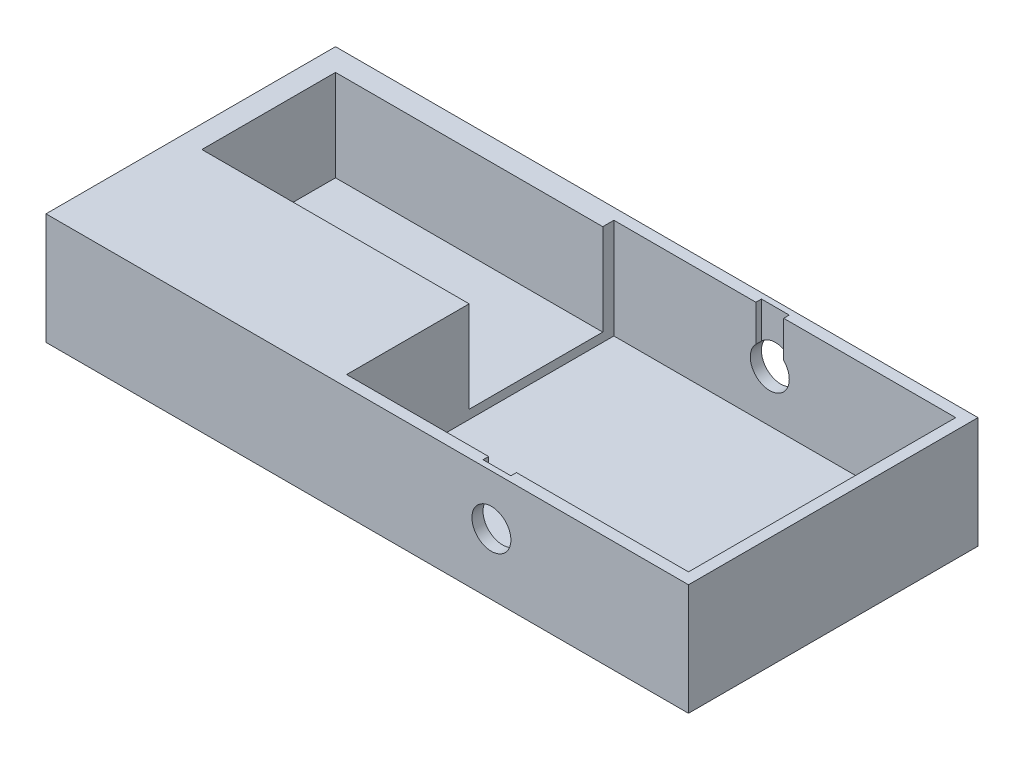
SolidWorks part; units mm, degrees
ref_plane "Front" through (0, 0, 0) normal (0, 0, 1) x (1, 0, 0)
ref_plane "Top" through (0, 0, 0) normal (0, 1, 0) x (1, 0, 0)
ref_plane "Right" through (0, 0, 0) normal (1, 0, 0) x (0, 0, -1)
sketch "Sketch1" plane through (0, 0, 0) normal (0, 1, 0) x (1, 0, 0)
  line L1 (-41.529, 33.02) -> (41.529, 33.02)
  line L2 (-41.529, 33.02) -> (-41.529, -33.02)
  line L3 (-41.529, -33.02) -> (41.529, -33.02)
  line L4 (41.529, 33.02) -> (41.529, -33.02)
  line L5 (-41.529, 33.02) -> (41.529, -33.02) construction
  line L6 (-41.529, -33.02) -> (41.529, 33.02) construction
  line L7 (-38.989, 30.48) -> (38.989, 30.48)
  line L8 (-38.989, 30.48) -> (-38.989, -30.48)
  line L9 (-38.989, -30.48) -> (38.989, -30.48)
  line L10 (38.989, 30.48) -> (38.989, -30.48)
  line L11 (-38.989, 30.48) -> (38.989, -30.48) construction
  line L12 (-38.989, -30.48) -> (38.989, 30.48) construction
  point P0 (0, 0)
  point P6 (0, 0)
  dimension "D1" = 66.04
  dimension "D2" = 83.058
  dimension "D3" = 60.96
  dimension "D4" = 77.978
extrude "pcb-base" add sketch "Sketch1" along normal blind 2.54 contours L8 L7 L10 L9
extrude "pcb-wall" add sketch "Sketch1<4>" along normal blind 25.4
sketch "Sketch1<4>" plane through (0, 0, 0) normal (0, 1, 0) x (1, 0, 0) same geometry as "Sketch1"
sketch "Sketch2" plane through (-41.529, 0, 0) normal (-1, 0, 0) x (0, 0, 1)
  line L1 (-27.94, 4.572) -> (2.54, 4.572)
  line L5 (-27.94, 25.4) -> (-27.94, 4.572)
  line L6 (2.54, 25.4) -> (33.02, 25.4)
  line L7 (33.02, 25.4) -> (33.02, 0) construction
  line L9 (-33.02, 0) -> (33.02, 0) construction
  line L11 (2.54, 4.572) -> (2.54, 25.4)
  line L13 (-33.02, 25.4) -> (33.02, 25.4) construction
  line L14 (33.02, 25.4) -> (33.02, 0)
  line L15 (-33.02, 0) -> (33.02, 0)
  line L16 (33.02, 0) -> (33.02, 25.4)
  line L17 (33.02, 25.4) -> (-33.02, 25.4)
  line L18 (-33.02, 25.4) -> (-33.02, 0)
  line L19 (-33.02, 0) -> (33.02, 0)
  line L23 (-33.02, 25.4) -> (-33.02, 0)
  line L24 (-27.94, 25.4) -> (-33.02, 25.4)
  point P0 (-12.7, 13.462)
  dimension "D1" = 5.08
  dimension "D2" = 30.48
  dimension "0.175" = 4.572
  dimension "D5" = 0
sketch "Sketch3" plane through (0, 0, -30.48) normal (0, 0, 1) x (1, 0, 0)
  line L0 (-38.989, 25.4) -> (-38.989, 2.54) construction
  line L2 (-6.604, 13.97) -> (-0.254, 13.97)
  line L3 (38.989, 25.4) -> (-38.989, 25.4) construction
  line L4 (-6.604, 13.97) -> (-6.604, 25.4)
  line L5 (-6.604, 25.4) -> (-0.254, 25.4)
  line L6 (-0.254, 13.97) -> (-0.254, 25.4)
  line L7 (-6.604, 13.97) -> (-0.254, 25.4) construction
  line L8 (-6.604, 25.4) -> (-0.254, 13.97) construction
  circle A0 centre (-3.429, 13.97) radius 4.445
  point P7 (-3.429, 19.685)
  line M4 (38.989, 25.4) -> (-38.989, 25.4)
  dimension "D2" = 8.89
  dimension "D1" = 35.56
  dimension "D3" = 11.43
  dimension "D4" = 6.35
sketch "Sketch4" plane through (0, 0, 30.48) normal (0, 0, -1) x (-1, 0, 0)
  line L0 (38.989, 25.4) -> (-38.989, 25.4) construction
  line L1 (0.254, 25.4) -> (6.604, 25.4)
  line L2 (0.254, 25.4) -> (0.254, 13.97)
  line L3 (0.254, 13.97) -> (6.604, 13.97)
  line L4 (6.604, 25.4) -> (6.604, 13.97)
  line L5 (0.254, 25.4) -> (6.604, 13.97) construction
  line L6 (0.254, 13.97) -> (6.604, 25.4) construction
  line L7 (41.529, 25.4) -> (41.529, 0) construction
  line L8 (-41.529, 25.4) -> (-41.529, 0) construction
  circle A0 centre (3.429, 13.97) radius 4.445
  point P2 (3.429, 19.685)
  line M4 (38.989, 25.4) -> (-38.989, 25.4)
  dimension "D1" = 8.89
  dimension "D2" = 6.35
  dimension "D3" = 3.175
extrude "lid-hole-1" cut sketch "Sketch4" against normal blind 3.81 contours L2 A0 L4 L3 | L4 A0 L2 L3 region at (-3.429, 16.004, 30.48) region at (-3.429, 12.5426, 30.48)
extrude "hole-slide-1" cut sketch "Sketch4<6>" against normal blind 1.27 contours A0 L4 L2 M4 region at (-3.429, 21.6904, 30.48)
sketch "Sketch4<6>" plane through (0, 0, 30.48) normal (0, 0, -1) x (-1, 0, 0) same geometry as "Sketch4"
extrude "lid-hole-2" cut sketch "Sketch3" against normal blind 3.81 contours L4 A0 L6 L2 | L6 A0 L4 L2 region at (-3.429, 16.004, -30.48) region at (-3.429, 12.5426, -30.48)
extrude "hole-slide-2" cut sketch "Sketch3<5>" against normal blind 1.27 contours A0 L6 L4 M4 region at (-3.429, 21.6904, -30.48)
sketch "Sketch3<5>" plane through (0, 0, -30.48) normal (0, 0, 1) x (1, 0, 0) same geometry as "Sketch3"
extrude "battery-compartment" add sketch "Sketch2" along normal blind 60.96
sketch "Sketch5" plane through (-102.489, 0, 0) normal (-1, 0, 0) x (0, 0, 1)
  line L1 (-33.02, 25.4) -> (33.02, 25.4)
  line L2 (-33.02, 25.4) -> (-33.02, 0)
  line L3 (-33.02, 0) -> (33.02, 0)
  line L4 (33.02, 25.4) -> (33.02, 0)
extrude "back-wall" add sketch "Sketch5" along normal blind 2.54 and the other way blind 2.54
sketch "Sketch8" plane through (-41.529, 0, 0) normal (-1, 0, 0) x (0, 0, 1)
  line L0 (2.54, 4.572) -> (-27.94, 4.572) construction
  line L1 (-27.94, 25.4) -> (2.54, 25.4)
  line L2 (-27.94, 25.4) -> (-27.94, 4.572)
  line L3 (-27.94, 4.572) -> (2.54, 4.572)
  line L4 (2.54, 25.4) -> (2.54, 4.572)
extrude "pcb-gap" cut sketch "Sketch8" against normal blind 2.54
